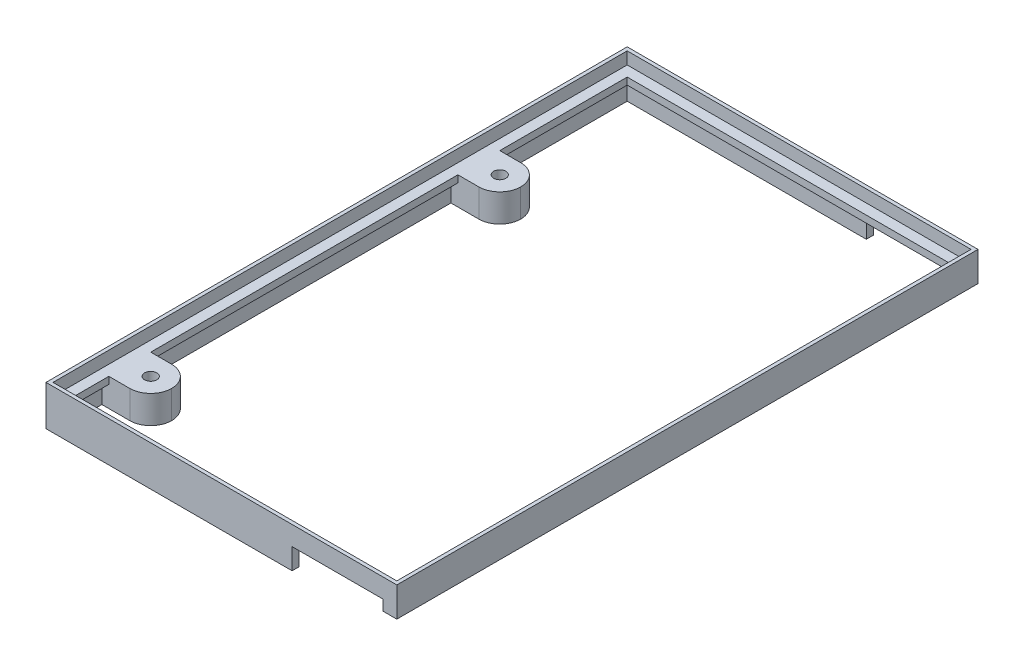
SolidWorks part; units mm, degrees
ref_plane "Front Plane" through (0, 0, 0) normal (0, 0, 1) x (1, 0, 0)
ref_plane "Top Plane" through (0, 0, 0) normal (0, 1, 0) x (1, 0, 0)
ref_plane "Right Plane" through (0, 0, 0) normal (1, 0, 0) x (0, 0, -1)
ref_plane "Plane1" through (0, -1, 0) normal (0, 1, 0) x (1, 0, 0)
sketch "Sketch2" plane through (0, 0, 0) normal (0, 1, 0) x (1, 0, 0)
  line L0 (-50.25, 83.25) -> (50.25, 83.25)
  line L1 (-49.25, 82.25) -> (49.25, 82.25)
  line L2 (-49.25, 82.25) -> (-49.25, -82.25)
  line L3 (-49.25, -82.25) -> (49.25, -82.25)
  line L4 (49.25, 82.25) -> (49.25, -82.25)
  line L5 (-49.25, 82.25) -> (49.25, -82.25) construction
  line L6 (-49.25, -82.25) -> (49.25, 82.25) construction
  line L7 (50.25, 83.25) -> (50.25, -83.25)
  line L8 (-50.25, -83.25) -> (50.25, -83.25)
  line L9 (-50.25, 83.25) -> (-50.25, -83.25)
  point P0 (0, 0)
  dimension "D1" = 98.5
  dimension "D2" = 164.5
  dimension "D3" = 1
extrude "DIAPLAY RING" add sketch "Sketch2" along normal blind 3.5
sketch "Sketch3" plane through (0, 0, 0) normal (0, 1, 0) x (1, 0, 0)
  line L0 (-50.25, 83.25) -> (50.25, 83.25) construction
  line L1 (50.25, 83.25) -> (50.25, -83.25) construction
  line L2 (-50.25, -83.25) -> (50.25, -83.25) construction
  line L3 (-50.25, 83.25) -> (-50.25, -83.25) construction
  line L4 (-50.25, 83.25) -> (50.25, 83.25)
  line L5 (50.25, 83.25) -> (50.25, -83.25)
  line L6 (-50.25, -83.25) -> (50.25, -83.25)
  line L7 (-50.25, 83.25) -> (-50.25, -83.25)
  line L8 (-46.25, 79.25) -> (-46.25, -79.25)
  line L9 (-46.25, -79.25) -> (46.25, -79.25)
  line L10 (46.25, 79.25) -> (46.25, -79.25)
  line L11 (-46.25, 79.25) -> (46.25, 79.25)
  dimension "D1" = 4
extrude "DISPLAY LIP" add sketch "Sketch3" against normal blind 2
sketch "Sketch4" plane through (0, 0, 0) normal (0, 1, 0) x (1, 0, 0)
  line L0 (-50.25, 83.25) -> (-50.25, -83.25) construction
  line L1 (-50.25, -57.25) -> (-34.25, -57.25)
  line L2 (-50.25, -57.25) -> (-50.25, -69.25)
  line L3 (-50.25, -69.25) -> (-34.25, -69.25)
  line L4 (-34.25, -57.25) -> (-34.25, -69.25)
  line L5 (49.25, 82.25) -> (49.25, -82.25) construction
  line L6 (49.25, -57.25) -> (33.25, -57.25) construction
  line L7 (49.25, -57.25) -> (49.25, -69.25) construction
  line L8 (49.25, -69.25) -> (33.25, -69.25) construction
  line L9 (33.25, -57.25) -> (33.25, -69.25) construction
  line L10 (-50.25, -83.25) -> (50.25, -83.25) construction
  line L11 (50.25, 83.25) -> (50.25, -83.25) construction
  line L12 (-50.25, 42.75) -> (-34.25, 42.75)
  line L13 (-50.25, 42.75) -> (-50.25, 30.75)
  line L14 (-50.25, 30.75) -> (-34.25, 30.75)
  line L15 (-34.25, 42.75) -> (-34.25, 30.75)
  line L16 (50.25, 42.75) -> (34.25, 42.75) construction
  line L17 (50.25, 42.75) -> (50.25, 30.75) construction
  line L18 (50.25, 30.75) -> (34.25, 30.75) construction
  line L19 (34.25, 42.75) -> (34.25, 30.75) construction
  circle A0 centre (-40.25, 36.75) radius 1.75
  circle A1 centre (40.25, 36.75) radius 1.75 construction
  circle A2 centre (39.25, -63.25) radius 1.75 construction
  circle A3 centre (-40.25, -63.25) radius 1.75
  point P33 (-34.25, 36.75)
  point P35 (34.25, 36.75)
  point P37 (33.25, -63.25)
  point P39 (-34.25, -63.25)
  dimension "D9" = 3.5
  dimension "D1" = 16
  dimension "D2" = 12
  dimension "D3" = 100
  dimension "D4" = 14
  dimension "D5" = 6
  dimension "D6" = 6
  dimension "D7" = 6
  dimension "D8" = 6
extrude "DISPLAY MOUNTING TABS" add sketch "Sketch4" against normal blind 8
fillet "Fillet1" radius 6 4 edges at (-34.25, -4, 57.25) (-34.25, -4, 69.25) (-34.25, -4, -42.75) (-34.25, -4, -30.75)
sketch "Sketch7" plane through (0, -1, 0) normal (0, 1, 0) x (1, 0, 0)
  line L0 (-50.25, 83.25) -> (-50.25, -83.25) construction
  line L1 (-50.25, -83.25) -> (50.25, -83.25) construction
  line L2 (50.25, 83.25) -> (50.25, -83.25) construction
  line L3 (-50.25, 83.25) -> (50.25, 83.25) construction
  line L4 (-50.25, 83.25) -> (-50.25, -83.25)
  line L5 (-50.25, -83.25) -> (50.25, -83.25)
  line L6 (50.25, 83.25) -> (50.25, -83.25)
  line L7 (-50.25, 83.25) -> (50.25, 83.25)
  line L8 (-48.25, 81.25) -> (-48.25, -81.25)
  line L9 (-48.25, -81.25) -> (48.25, -81.25)
  line L10 (48.25, 81.25) -> (48.25, -81.25)
  line L11 (-48.25, 81.25) -> (48.25, 81.25)
  dimension "D1" = 2
extrude "PERIMETER EXTENSION FOR STRUCTURE" add sketch "Sketch7" against normal up to surface (7 mm away) up to face at (-40.25, -8, -35)
sketch "Sketch8" plane through (0, -8, 0) normal (0, -1, 0) x (1, 0, 0)
  line L0 (-50.25, 83.25) -> (50.25, 83.25) construction
  line L1 (50.25, -83.25) -> (50.25, 83.25) construction
  line L2 (-50.25, -83.25) -> (50.25, -83.25) construction
  line L4 (25.25, 83.25) -> (50.25, 83.25)
  line L5 (50.25, -83.25) -> (50.25, 83.25)
  line L6 (25.25, -83.25) -> (50.25, -83.25)
  line L8 (25.25, 81.25) -> (48.25, 81.25)
  line L9 (48.25, -81.25) -> (48.25, 81.25)
  line L10 (25.25, -81.25) -> (48.25, -81.25)
  line L12 (25.25, 81.25) -> (25.25, 83.25)
  line L13 (25.25, -83.25) -> (25.25, -81.25)
  line L14 (-48.25, -81.25) -> (48.25, -81.25) construction
  line L15 (-50.25, -83.25) -> (50.25, -83.25) construction
  line L16 (-50.25, -83.25) -> (-50.25, 83.25) construction
  line L17 (-48.25, -81.25) -> (-48.25, 81.25) construction
  line L18 (-48.25, 81.25) -> (48.25, 81.25) construction
  line L19 (-50.25, 83.25) -> (50.25, 83.25) construction
  dimension "D2" = 25
  dimension "D3" = 25
  dimension "D1" = 2
extrude "PERIMETER EXTENSION FOR CAR TRIM" add sketch "Sketch8" along normal blind 2
sketch "Sketch9" plane through (0, -1, 0) normal (0, 1, 0) x (1, 0, 0)
  line L0 (-50.25, -83.25) -> (50.25, -83.25) construction
  line L1 (50.25, 83.25) -> (46.25, 83.25)
  line L2 (50.25, 83.25) -> (50.25, -83.25)
  line L3 (50.25, -83.25) -> (46.25, -83.25)
  line L4 (46.25, 83.25) -> (46.25, -83.25)
  dimension "D1" = 4
extrude "MATERIAL ADDITION FOR DISPLAY MOUNTING SLOT" add sketch "Sketch9" against normal blind 4
sketch "Sketch10" plane through (46.25, 0, 0) normal (-1, 0, 0) x (0, 0, 1)
  line L1 (-75, -3.125) -> (75, -3.125)
  line L2 (-75, -3.125) -> (-75, -1.875)
  line L3 (-75, -1.875) -> (75, -1.875)
  line L4 (75, -3.125) -> (75, -1.875)
  point P4 (0, -1.875)
  point P6 (-75, -2.5)
  dimension "D1" = 150
  dimension "D2" = 1.25
  dimension "D3" = 2.5
extrude "DISPLAY MOUNTING SLOT" cut sketch "Sketch10" against normal blind 3
ref_plane "SHIFTER SCREW HOLE PLANE" through (0, -55, 0) normal (0, 1, 0) x (1, 0, 0)
sketch "Sketch5" plane through (0, -55, 0) normal (0, 1, 0) x (1, 0, 0)
  point P0 (-50, 93)
  point P1 (12, 93)
  dimension "D1" = 93
  dimension "D2" = 12
  dimension "D3" = 50
sketch "Sketch6" plane through (0, -55, 0) normal (0, 1, 0) x (1, 0, 0)
  line L0 (-50, 93) -> (12, 93) construction
  line L1 (-50, 106.5) -> (12, 106.5)
  line L2 (-50, 79.5) -> (12, 79.5)
  arc A0 (-50, 106.5) -> (-50, 79.5) centre (-50, 93) ccw
  arc A1 (12, 79.5) -> (12, 106.5) centre (12, 93) ccw
  circle A2 centre (-50, 93) radius 1.75
  circle A3 centre (12, 93) radius 1.75
  point P4 (-19, 93)
  dimension "D1" = 13.5
  dimension "D2" = 3.5
extrude "SHIFTER SCREW IF" add sketch "Sketch6" against normal blind 3
sketch "Sketch11" plane through (0, 0, 0) normal (0, 0, 1) x (1, 0, 0)
  line L0 (50.25, -10) -> (50.25, -5)
  line L1 (50.25, 3.5) -> (50.25, -10) construction
  line L2 (50.25, -5) -> (46.25, -5)
  line L3 (46.25, -5) -> (46.25, -2)
  line L4 (46.25, -2) -> (20.25, -2)
  line L5 (20.25, -2) -> (20.25, -10)
  line L6 (20.25, -10) -> (50.25, -10)
  line L7 (48.25, -5) -> (46.25, -5) construction
  line L8 (46.25, -5) -> (46.25, -2) construction
  line L9 (46.25, -2) -> (-48.25, -2) construction
  dimension "D1" = 30
extrude "Cut-Extrude2" cut sketch "Sketch11" against normal through all both and the other way through all
delete or keep bodies "Body-Delete/Keep 1" type delete bodies bodies 104
